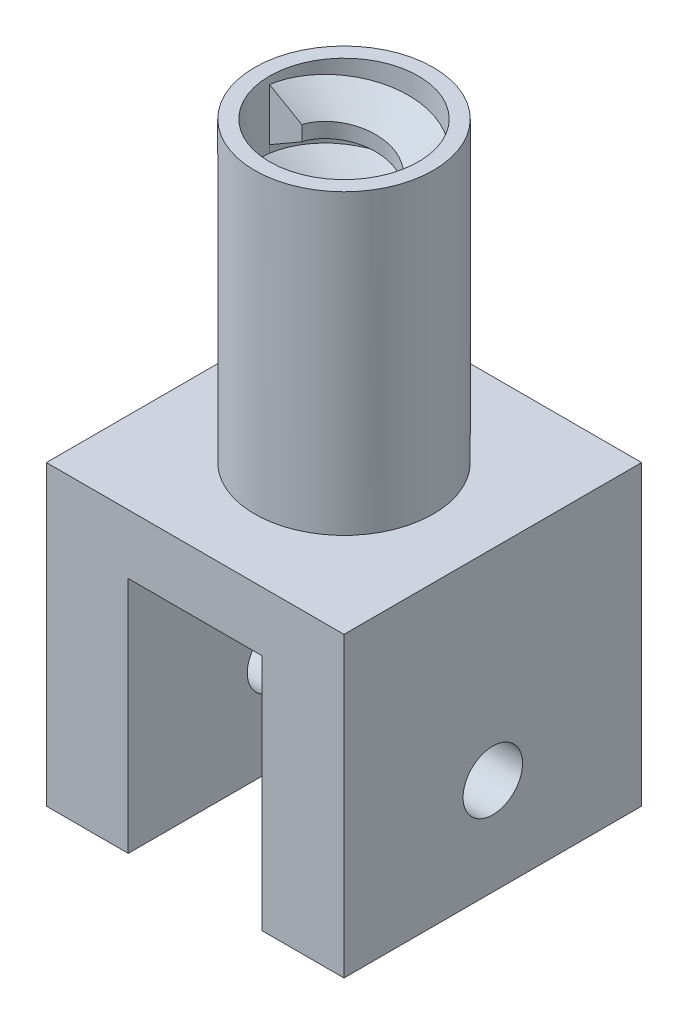
SolidWorks part; units mm, degrees
ref_plane "Front Plane" through (0, 0, 0) normal (0, 0, 1) x (1, 0, 0)
ref_plane "Top Plane" through (0, 0, 0) normal (0, 1, 0) x (1, 0, 0)
ref_plane "Right Plane" through (0, 0, 0) normal (1, 0, 0) x (0, 0, -1)
sketch "Sketch1" plane through (0, 0, 0) normal (0, 1, 0) x (1, 0, 0)
  circle A0 centre (0, 0) radius 6
  circle A1 centre (0, 0) radius 5
  dimension "D1" = 12
  dimension "D2" = 10
extrude "Boss-Extrude1" add sketch "Sketch1" along normal blind 20
thread "Thread1" pitch 4 method extrude profile "Thread Profile1" start angle 0, offset 0.5, length 0, pitch 4, diameter 10
ref_plane "Plane1" through (-5, 19.5, 0) normal (0, 0, 1) x (-1, 0, 0)
sketch "Thread Profile1" plane through (-5, 19.5, 0) normal (0, 0, 1) x (-1, 0, 0)
  line L0 (0, 0) -> (0, 4) construction
  line L11 (0, 0) -> (0, 3.5)
  line L12 (0, 3.5) -> (-2.1651, 2.25)
  line L13 (-2.1651, 2.25) -> (-2.1651, 1.25)
  line L15 (-2.1651, 1.25) -> (0, 0)
  line L17 (-2.1651, 1.75) -> (0, 1.75) construction
  point P2 (0, 0)
  dimension "Pitch" = 4
  dimension "Profile_Angle" = 60
  dimension "Profile_Land" = 1
  dimension "Profile_Height" = 2.1651
sketch "Sketch6" plane through (0, 0, 0) normal (0, -1, 0) x (1, 0, 0)
  line L0 (0, 0) -> (10, 0) construction
  line L5 (0, 0) -> (-10, 0) construction
  line L6 (0, 0) -> (0, 10) construction
  line L7 (0, 0) -> (0, -10) construction
  line L9 (-10, 10) -> (-10, -10)
  line L10 (-10, -10) -> (10, -10)
  line L11 (10, -10) -> (10, 10)
  line L13 (-10, 10) -> (10, 10)
  point P3 (0, 15.0296)
  dimension "D1" = 20
extrude "Boss-Extrude2" add sketch "Sketch6" along normal blind 4
sketch "Sketch7" plane through (0, 0, 10) normal (0, 0, 1) x (1, 0, 0)
  line L0 (-10, -4) -> (-10, 0) construction
  line L1 (10, 0) -> (4.5, 0)
  line L2 (10, 0) -> (10, -20)
  line L3 (10, -20) -> (4.5, -20)
  line L4 (4.5, 0) -> (4.5, -20)
  line L5 (-10, 0) -> (-4.5, 0)
  line L6 (-10, 0) -> (-10, -20)
  line L7 (-10, -20) -> (-4.5, -20)
  line L8 (-4.5, 0) -> (-4.5, -20)
  line L9 (10, 0) -> (-10, 0) construction
  dimension "D1" = 9
  dimension "D2" = 20
extrude "Boss-Extrude3" add sketch "Sketch7" against normal up to surface (20 mm away) up to face at (0, -2, -10)
sketch "Sketch8" plane through (10, 0, 0) normal (1, 0, 0) x (0, 0, -1)
  line L0 (10, -13.5) -> (-10, -13.5) construction
  line L1 (10, -20) -> (10, 0) construction
  line L2 (-10, -20) -> (-10, 0) construction
  line L3 (10, -20) -> (-10, -20) construction
  circle A0 centre (0, -13.5) radius 2
  dimension "D2" = 4
  dimension "D1" = 6.5
extrude "Cut-Extrude1" cut sketch "Sketch8" against normal through all
